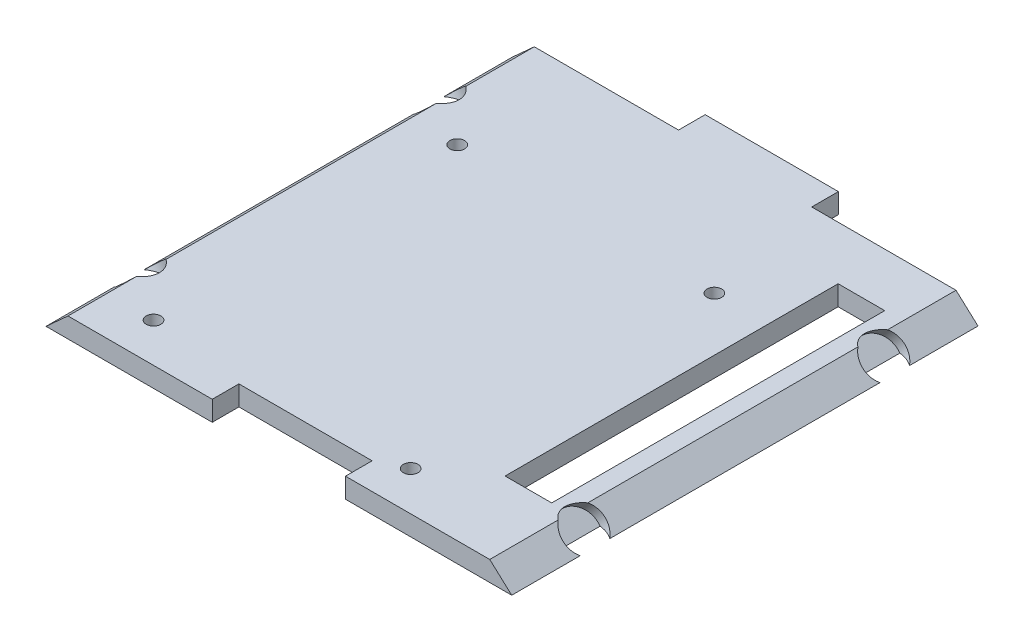
SolidWorks part; units mm, degrees
ref_plane "Front Plane" through (0, 0, 0) normal (0, 0, 1) x (1, 0, 0)
ref_plane "Top Plane" through (0, 0, 0) normal (0, 1, 0) x (1, 0, 0)
ref_plane "Right Plane" through (0, 0, 0) normal (1, 0, 0) x (0, 0, -1)
sketch "Sketch1" plane through (0, 0, 0) normal (0, 0, 1) x (1, 0, 0)
  line L0 (0, 0) -> (0, 44.45) construction
  line L1 (-40.2039, 5.9378) -> (40.2039, 5.9378)
  line L2 (-44.399, 2.1278) -> (44.399, 2.1278)
  line L3 (-40.2039, 5.9378) -> (-44.399, 2.1278)
  line L4 (40.2039, 5.9378) -> (44.399, 2.1278)
  arc A0 (44.399, 2.1278) -> (-44.399, 2.1278) centre (0, 0) ccw construction
  arc A1 (40.2039, 5.9378) -> (-40.2039, 5.9378) centre (0, 0) ccw construction
  dimension "D1" = 88.9
  dimension "D2" = 3.81
  dimension "D3" = 3.81
extrude "Boss-Extrude1" add sketch "Sketch1" along normal blind 88.9
sketch "Sketch2" plane through (0, 2.1278, 0) normal (0, -1, 0) x (1, 0, 0)
  line L0 (0, 88.9) -> (0, 0) construction
  line L1 (-34.417, 85.09) -> (20.701, 85.09) construction
  line L2 (-34.417, 85.09) -> (-34.417, 0) construction
  line L3 (-34.417, 0) -> (20.701, 0) construction
  line L4 (20.701, 85.09) -> (20.701, 0) construction
  line L5 (-44.399, 88.9) -> (44.399, 88.9) construction
  line L6 (-44.399, 0) -> (44.399, 0) construction
  line L7 (-34.417, 42.545) -> (20.701, 42.545) construction
  line L8 (-6.858, 85.09) -> (-6.858, 0) construction
  circle A0 centre (-31.369, 81.43) radius 1.397
  circle A1 centre (17.653, 23.518) radius 1.397
  circle A2 centre (-31.369, 23.518) radius 1.397
  circle A3 centre (17.653, 81.43) radius 1.397
  point P10 (-6.858, 85.09)
  dimension "D4" = 2.794
  dimension "D7" = 2.794
  dimension "D8" = 57.912
  dimension "D9" = 23.518
  dimension "D5" = 49.022
  dimension "D1" = 6.858
  dimension "D2" = 85.09
  dimension "D3" = 3.81
  dimension "D6" = 55.118
extrude "Cut-Extrude1" cut sketch "Sketch2" against normal through all
sketch "Sketch3" plane through (0, 2.1278, 0) normal (0, -1, 0) x (1, 0, 0)
  line L0 (0, 88.9) -> (0, 0) construction
  line L1 (-44.399, 88.9) -> (44.399, 88.9) construction
  line L2 (-44.399, 0) -> (44.399, 0) construction
  line L3 (0, 44.45) -> (44.399, 44.45) construction
  line L4 (-12.7, 88.9) -> (12.7, 88.9)
  line L5 (-12.7, 88.9) -> (-12.7, 83.82)
  line L6 (-12.7, 83.82) -> (12.7, 83.82)
  line L7 (12.7, 88.9) -> (12.7, 83.82)
  line L8 (44.399, 88.9) -> (44.399, 0) construction
  line L9 (0, 44.45) -> (-44.399, 44.45) construction
  line L10 (-44.399, 88.9) -> (-44.399, 0) construction
  line L11 (12.7, 0) -> (12.7, 5.08)
  line L12 (-12.7, 5.08) -> (12.7, 5.08)
  line L13 (-12.7, 0) -> (12.7, 0)
  line L14 (-12.7, 0) -> (-12.7, 5.08)
  point P10 (12.7, 86.36)
  dimension "D1" = 25.4
  dimension "D2" = 12.7
  dimension "D3" = 5.08
extrude "Cut-Extrude2" cut sketch "Sketch3" against normal through all
sketch "Sketch5" plane through (0, 2.1278, 0) normal (0, -1, 0) x (1, 0, 0)
  line L0 (12.7, 0) -> (12.7, 5.08) construction
  line L1 (12.7, 5.08) -> (-12.7, 5.08)
  line L2 (12.7, 5.08) -> (12.7, -5.08)
  line L3 (12.7, -5.08) -> (-12.7, -5.08)
  line L4 (-12.7, 5.08) -> (-12.7, -5.08)
  line L5 (12.7, 5.08) -> (-12.7, 5.08) construction
  dimension "D1" = 0
  dimension "D2" = 25.4
  dimension "D3" = 10.16
extrude "Boss-Extrude3" add sketch "Sketch5" against normal blind 3.81
sketch "Sketch6" plane through (0, 2.1278, 0) normal (0, -1, 0) x (1, 0, 0)
  line L0 (12.7, 88.9) -> (44.399, 88.9) construction
  line L1 (27.889, 73.66) -> (36.779, 73.66)
  line L2 (27.889, 73.66) -> (27.889, 10.16)
  line L3 (27.889, 10.16) -> (36.779, 10.16)
  line L4 (36.779, 73.66) -> (36.779, 10.16)
  line L5 (44.399, 88.9) -> (44.399, 0) construction
  dimension "D1" = 15.24
  dimension "D2" = 7.62
  dimension "D3" = 63.5
  dimension "D4" = 8.89
extrude "Cut-Extrude3" cut sketch "Sketch6" against normal through all
sketch "Sketch7" plane through (21.1272, 23.263, 0) normal (0.6723, 0.7403, 0) x (0.7403, -0.6723, 0)
  line L0 (28.6033, -88.9) -> (28.6033, 25.3146) construction
  line L1 (31.4368, -88.9) -> (25.7698, -88.9) construction
  line L2 (25.7698, -44.45) -> (31.987, -44.45) construction
  line L3 (25.7698, -88.9) -> (25.7698, 0) construction
  circle A0 centre (28.6033, -73.025) radius 4
  circle A1 centre (28.6033, -15.875) radius 4
  dimension "D1" = 8
  dimension "D2" = 28.575
extrude "Cut-Extrude4" cut sketch "Sketch7" against normal blind 2
sketch "Sketch8" plane through (-21.1272, 23.263, 0) normal (-0.6723, 0.7403, 0) x (0.7403, 0.6723, 0)
  line L0 (-28.6033, 0) -> (-28.6033, -88.7644) construction
  line L1 (-25.7698, 0) -> (-31.4368, 0) construction
  line L2 (-25.7698, -44.45) -> (-31.4368, -44.45) construction
  line L3 (-25.7698, -88.9) -> (-25.7698, 0) construction
  line L4 (-31.4368, -88.9) -> (-31.4368, 0) construction
  circle A0 centre (-28.6033, -15.875) radius 4
  circle A1 centre (-28.6033, -73.025) radius 4
  dimension "D1" = 8
  dimension "D2" = 28.575
extrude "Cut-Extrude5" cut sketch "Sketch8" against normal blind 2
